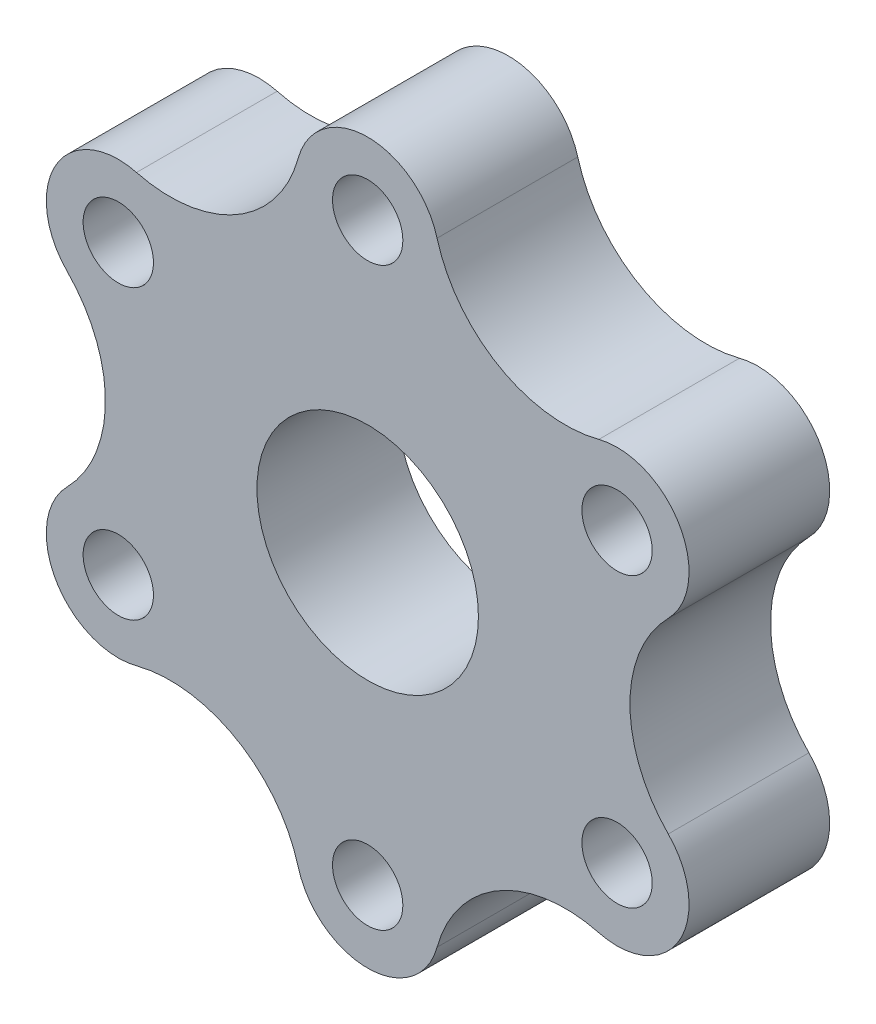
SolidWorks part; units mm, degrees
material "6061-T6 (SS)"
ref_plane "Front Plane" through (0, 0, 0) normal (0, 0, 1) x (1, 0, 0)
ref_plane "Top Plane" through (0, 0, 0) normal (0, 1, 0) x (1, 0, 0)
ref_plane "Right Plane" through (0, 0, 0) normal (1, 0, 0) x (0, 0, -1)
sketch "Sketch1" plane through (0, 0, 0) normal (0, 0, 1) x (1, 0, 0)
  circle A0 centre (0, 0) radius 40 construction
  circle A1 centre (0, 0) radius 35 construction
  circle A2 centre (0, 0) radius 10
  arc A3 (6.268, 27.7213) -> (-6.268, 27.7213) centre (0, 26) ccw
  arc A4 (27.1413, 8.4324) -> (20.8734, 19.2888) centre (22.5167, 13) ccw
  arc A5 (20.8734, -19.2888) -> (27.1413, -8.4324) centre (22.5167, -13) ccw
  arc A6 (-6.268, -27.7213) -> (6.268, -27.7213) centre (0, -26) ccw
  arc A7 (-27.1413, -8.4324) -> (-20.8734, -19.2888) centre (-22.5167, -13) ccw
  arc A8 (-20.8734, 19.2888) -> (-27.1413, 8.4324) centre (-22.5167, 13) ccw
  arc A9 (-20.8734, 19.2888) -> (-6.268, 27.7213) centre (-17.8396, 30.899) ccw
  arc A10 (6.268, 27.7213) -> (20.8734, 19.2888) centre (17.8396, 30.899) ccw
  arc A11 (27.1413, 8.4324) -> (27.1413, -8.4324) centre (35.6791, 0) ccw
  arc A12 (20.8734, -19.2888) -> (6.268, -27.7213) centre (17.8396, -30.899) ccw
  arc A13 (-6.268, -27.7213) -> (-20.8734, -19.2888) centre (-17.8396, -30.899) ccw
  arc A14 (-27.1413, -8.4324) -> (-27.1413, 8.4324) centre (-35.6791, 0) ccw
  arc A15 (-27.1413, 8.4324) -> (-20.8734, 19.2888) centre (-22.5167, 13) ccw construction
  arc A16 (-6.268, 27.7213) -> (6.268, 27.7213) centre (0, 26) ccw construction
  arc A17 (20.8734, 19.2888) -> (27.1413, 8.4324) centre (22.5167, 13) ccw construction
  arc A18 (27.1413, -8.4324) -> (20.8734, -19.2888) centre (22.5167, -13) ccw construction
  arc A19 (6.268, -27.7213) -> (-6.268, -27.7213) centre (0, -26) ccw construction
  arc A20 (-20.8734, -19.2888) -> (-27.1413, -8.4324) centre (-22.5167, -13) ccw construction
  circle A21 centre (0, 26) radius 3.175
  circle A22 centre (22.5167, 13) radius 3.175
  circle A23 centre (22.5167, -13) radius 3.175
  circle A24 centre (0, -26) radius 3.175
  circle A25 centre (-22.5167, -13) radius 3.175
  circle A26 centre (-22.5167, 13) radius 3.175
  point P19 (0, 0)
  point P38 (0, 0)
  point P44 (0, 0)
  dimension "D1" = 80
  dimension "D2" = 70
  dimension "D3" = 20
  dimension "D4" = 13
  dimension "D7" = 12
  dimension "D9" = 6.35
  dimension "D5" = 26
  dimension "D6" = 6
  dimension "D8" = 6
  dimension "D10" = 6
extrude "Boss-Extrude1" add sketch "Sketch1" along normal mid plane 12.7
equation "\"D9@Sketch1\"=0.25in"
equation "\"D1@Boss-Extrude1\"=0.5in"
